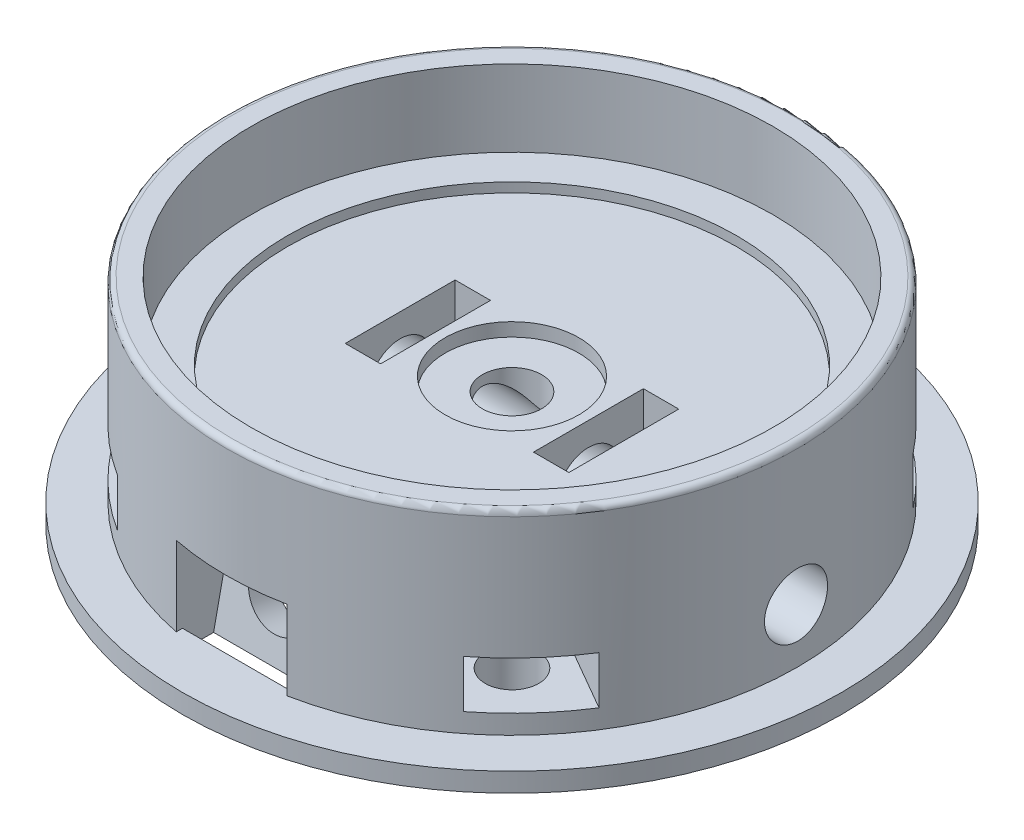
SolidWorks part; units mm, degrees
ref_plane "Front Plane" through (0, 0, 0) normal (0, 0, 1) x (1, 0, 0)
ref_plane "Top Plane" through (0, 0, 0) normal (0, 1, 0) x (1, 0, 0)
ref_plane "Right Plane" through (0, 0, 0) normal (1, 0, 0) x (0, 0, -1)
sketch "Sketch1" plane through (0, 0, 0) normal (0, 1, 0) x (1, 0, 0)
  circle A0 centre (0, 0) radius 14.95
  dimension "D1" = 29.9
extrude "Boss-Extrude1" add sketch "Sketch1" along normal blind 6.2
sketch "Sketch2" plane through (0, 6.2, 0) normal (0, 1, 0) x (1, 0, 0)
  circle A0 centre (0, 0) radius 11.75
  dimension "D1" = 23.5
extrude "Cut-Extrude1" cut sketch "Sketch2" against normal blind 0.5
sketch "Sketch3" plane through (0, 6.2, 0) normal (0, 1, 0) x (1, 0, 0)
  circle A0 centre (0, 0) radius 13.65
  circle A1 centre (0, 0) radius 14.95
  circle A2 centre (0, 0) radius 14.95 construction
  dimension "D1" = 27.3
extrude "Boss-Extrude2" add sketch "Sketch3" along normal blind 4
fillet "Fillet1" radius 0.3 1 edges at (0, 10.2, 14.95)
sketch "Sketch4" plane through (0, 5.7, 0) normal (0, 1, 0) x (1, 0, 0)
  circle A0 centre (0, 0) radius 1.55
  dimension "D1" = 3.1
extrude "Cut-Extrude2" cut sketch "Sketch4" against normal through all
ref_plane "Plane1" through (4, 0, 0) normal (1, 0, 0) x (0, 0, -1)
sketch "Sketch5" plane through (0, 0, 0) normal (1, 0, 0) x (0, 0, -1)
  line L1 (1.55, 5.7) -> (-1.55, 5.7) construction
  line L2 (-2.875, -0.05) -> (2.875, -0.05) construction
  line L3 (-2.875, -0.05) -> (-2.875, 5.7) construction
  line L4 (-2.875, 5.7) -> (2.875, 5.7) construction
  line L5 (2.875, -0.05) -> (2.875, 5.7) construction
  line L6 (-2.875, -0.05) -> (2.875, 5.7) construction
  line L7 (-2.875, 5.7) -> (2.875, -0.05) construction
  circle A0 centre (0, 2.825) radius 1.65
  dimension "D1" = 3.3
  dimension "D2" = 5.75
extrude "Cut-Extrude3" cut sketch "Sketch5" along normal through all
sketch "Sketch6" plane through (0, 0, 0) normal (0, -1, 0) x (1, 0, 0)
  circle A0 centre (0, 0) radius 1.55 construction
  circle A1 centre (0, 0) radius 1.55
  circle A2 centre (0, 0) radius 17.25
  dimension "D1" = 34.5
extrude "Boss-Extrude3" add sketch "Sketch6" along normal blind 1
sketch "Sketch7" plane through (4, 0, 0) normal (1, 0, 0) x (0, 0, -1)
  line L7 (-2.875, 5.7) -> (2.875, 5.7)
  line L8 (-2.875, 5.7) -> (-2.875, -0.05)
  line L9 (-2.875, -0.05) -> (2.875, -0.05)
  line L10 (2.875, 5.7) -> (2.875, -0.05)
  line L11 (-2.875, 5.7) -> (2.875, -0.05) construction
  line L12 (-2.875, -0.05) -> (2.875, 5.7) construction
  point P1 (0, 2.825)
  dimension "D2" = 5.75
extrude "Cut-Extrude4" cut sketch "Sketch7" along normal blind 1.85
ref_axis "Axis1" through (0, 9.9, 0) along (0, -1, 0)
pattern_circular "CirPattern1" count 2 over 360 about axis through (0, 9.9, 0) along (0, -1, 0) of "Cut-Extrude4", "Cut-Extrude3"
ref_plane "Plane2" through (0, 0, 0) normal (0, 0, 1) x (0, -1, 0)
ref_plane "Plane3" through (0, 0, 12.5) normal (0, 0, 1) x (0, -1, 0)
sketch "Sketch11" plane through (0, 0, 12.5) normal (0, 0, 1) x (0, -1, 0)
  line L0 (0, 23.2225) -> (0, -23.2225) construction
  point P4 (0, 0)
ref_plane "Plane4" through (0, 2.5421, 11.9597) normal (0, 0.2079, 0.9781) x (-1, 0, 0)
sketch "Sketch9" plane through (0, 0.4189, 12.411) normal (0, 0.2079, 0.9781) x (0, -0.9781, 0.2079)
  line L0 (-11.8543, 0) -> (-2.1706, 0) construction
  line L2 (1.4283, 2.9) -> (-4.3717, 2.9) construction
  line L3 (1.4283, 2.9) -> (1.4283, -2.9) construction
  line L4 (1.4283, -2.9) -> (-4.3717, -2.9) construction
  line L5 (-4.3717, 2.9) -> (-4.3717, -2.9) construction
  line L6 (1.4283, 2.9) -> (-4.3717, -2.9) construction
  line L7 (1.4283, -2.9) -> (-4.3717, 2.9) construction
  line L8 (0.4283, 23.2225) -> (0.4283, -23.2225) construction
  circle A0 centre (-1.4717, 0) radius 1.65
  dimension "D2" = 3.3
  dimension "D1" = 5.8
  dimension "D3" = 1
extrude "Cut-Extrude5" cut sketch "Sketch9" along normal through all and the other way blind 2
sketch "Sketch10" plane through (0, 0, 12.5) normal (0, 0.2079, 0.9781) x (0, -0.9781, 0.2079)
  line L1 (1, 2.9) -> (-4.8, 2.9) construction
  line L2 (-4.8, 2.9) -> (-4.8, -2.9) construction
  line L3 (1, -2.9) -> (-4.8, -2.9) construction
  line L5 (1, 2.9) -> (-4.8, 2.9)
  line L6 (-4.8, 2.9) -> (-4.8, -2.9)
  line L7 (1, -2.9) -> (-4.8, -2.9)
  line L8 (1, 2.9) -> (3, 2.9)
  line L9 (3, 2.9) -> (3, -2.9)
  line L10 (3, -2.9) -> (1, -2.9)
  dimension "D1" = 2
extrude "Cut-Extrude6" cut sketch "Sketch10" along normal blind 1.8
ref_plane "Plane5" through (0, 2.2302, 10.4924) normal (0, 0.2079, 0.9781) x (-1, 0, 0)
sketch "Sketch13" plane through (0, 2.2302, 10.4924) normal (0, 0.2079, 0.9781) x (-1, 0, 0)
  line L0 (-2.4902, -0.2075) -> (-3.8756, 3.5989)
  line L1 (-3.8756, 3.5989) -> (3.8756, 3.5989)
  line L2 (3.8756, 3.5989) -> (2.4902, -0.2075)
  line L3 (0, 0.6989) -> (0, 3.5989) construction
  line L4 (-2.9, 3.5989) -> (2.9, 3.5989) construction
  circle A0 centre (0, 0.6989) radius 1.65 construction
  circle A1 centre (0, 0.6989) radius 1.65 construction
  circle A2 centre (0, 0.6989) radius 2.65 construction
  arc A3 (2.4902, -0.2075) -> (-2.4902, -0.2075) centre (0, 0.6989) cw
  dimension "D1" = 20
  dimension "D2" = 1
ref_plane "Plane6" through (0, 0, 0) normal (-1, 0, 0) x (0, -1, 0)
ref_plane "Plane7" through (0, 0, 14.95) normal (0, 0, 1) x (1, 0, 0)
sketch "Sketch14" plane through (0, 0, 0) normal (-1, 0, 0) x (0, -1, 0)
  line L0 (-3.1606, 10.2947) -> (3.2723, 0) construction
  line L3 (0.0673, 10.9808) -> (-3.1606, 10.2947) construction
  line L5 (-3.1606, 10.2947) -> (-0.9985, 0.1229) construction
  arc A0 (-3.1606, 10.2947) -> (3.2723, 0) centre (14.1981, 13.9844) ccw
  dimension "D1" = 70
sweep "Cut-Sweep1" cut profiles "Sketch13" path "Sketch14"
sketch "Sketch19" plane through (0, 0, 14.95) normal (0, 0, 1) x (1, 0, 0)
  line L0 (2.9, 5.0693) -> (-2.9, 5.0693) construction
  line L1 (2.9, 5.0693) -> (-2.9, 5.0693) construction
  line L2 (14.95, 0) -> (-14.95, 0) construction
  line L3 (2.9, 0) -> (-2.9, 0) construction
  line L4 (-2.9, 5.0693) -> (-2.9, 0) construction
  line L5 (2.9, 5.0693) -> (2.9, 0) construction
  line L6 (-2.9, 4.1501) -> (2.9, 4.1501)
  line L7 (2.9, 4.1501) -> (2.9, 0)
  line L8 (2.9, 0) -> (-2.9, 0)
  line L9 (-2.9, 0) -> (-2.9, 4.1501)
  spline S0 degree 3 poles (-0.1103, 0.7763) (0.2206, 0.7763) (0.4399, 0.8212) (0.8405, 0.99) (1.0254, 1.1159) (1.2535, 1.3495) (1.3227, 1.4364) (1.4409, 1.6192) (1.4907, 1.7158) (1.5713, 1.9192) (1.6018, 2.0256) (1.6413, 2.2393) (1.6508, 2.3478) (1.6481, 2.6782) (1.6047, 2.8939) (1.4812, 3.1989) (1.431, 3.2954) (1.313, 3.4783) (1.2443, 3.5654) (1.0179, 3.8015) (0.8351, 3.9301) (0.4362, 4.1039) (0.2169, 4.1502) (-0.1103, 4.15) (-0.221, 4.1383) (-0.434, 4.0932) (-0.5375, 4.06) (-0.8386, 3.9282) (-1.0184, 3.8015) (-1.2465, 3.5629) (-1.3137, 3.4773) (-1.4313, 3.2948) (-1.4822, 3.1968) (-1.5641, 2.9938) (-1.5952, 2.8896) (-1.6378, 2.6758) (-1.6492, 2.5653) (-1.6515, 2.2381) (-1.6108, 2.0182) (-1.4501, 1.6141) (-1.3285, 1.4262) (-1.1006, 1.193) (-1.0155, 1.1217) (-0.835, 0.9992) (-0.7396, 0.9473) (-0.5381, 0.8627) (-0.4321, 0.8302) (-0.2188, 0.7873) (-0.1103, 0.7763) (0.2206, 0.7763) (0.4399, 0.8212) knots -0.03125 -0.03125 0 0 0.0625 0.0625 0.125 0.125 0.15625 0.15625 0.1875 0.1875 0.21875 0.21875 0.25 0.25 0.3125 0.3125 0.34375 0.34375 0.375 0.375 0.4375 0.4375 0.5 0.5 0.53125 0.53125 0.5625 0.5625 0.625 0.625 0.65625 0.65625 0.6875 0.6875 0.71875 0.71875 0.75 0.75 0.8125 0.8125 0.875 0.875 0.90625 0.90625 0.9375 0.9375 0.96875 0.96875 1 1 1.0625 1.0625 1.125 only from (0, 0.7763) to (0, 0.7763) construction
  spline S1 degree 3 poles (-0.1103, 0.7763) (0.2206, 0.7763) (0.4399, 0.8212) (0.8405, 0.99) (1.0254, 1.1159) (1.2535, 1.3495) (1.3227, 1.4364) (1.4409, 1.6192) (1.4907, 1.7158) (1.5713, 1.9192) (1.6018, 2.0256) (1.6413, 2.2393) (1.6508, 2.3478) (1.6481, 2.6782) (1.6047, 2.8939) (1.4812, 3.1989) (1.431, 3.2954) (1.313, 3.4783) (1.2443, 3.5654) (1.0179, 3.8015) (0.8351, 3.9301) (0.4362, 4.1039) (0.2169, 4.1502) (-0.1103, 4.15) (-0.221, 4.1383) (-0.434, 4.0932) (-0.5375, 4.06) (-0.8386, 3.9282) (-1.0184, 3.8015) (-1.2465, 3.5629) (-1.3137, 3.4773) (-1.4313, 3.2948) (-1.4822, 3.1968) (-1.5641, 2.9938) (-1.5952, 2.8896) (-1.6378, 2.6758) (-1.6492, 2.5653) (-1.6515, 2.2381) (-1.6108, 2.0182) (-1.4501, 1.6141) (-1.3285, 1.4262) (-1.1006, 1.193) (-1.0155, 1.1217) (-0.835, 0.9992) (-0.7396, 0.9473) (-0.5381, 0.8627) (-0.4321, 0.8302) (-0.2188, 0.7873) (-0.1103, 0.7763) (0.2206, 0.7763) (0.4399, 0.8212) knots -0.03125 -0.03125 0 0 0.0625 0.0625 0.125 0.125 0.15625 0.15625 0.1875 0.1875 0.21875 0.21875 0.25 0.25 0.3125 0.3125 0.34375 0.34375 0.375 0.375 0.4375 0.4375 0.5 0.5 0.53125 0.53125 0.5625 0.5625 0.625 0.625 0.65625 0.65625 0.6875 0.6875 0.71875 0.71875 0.75 0.75 0.8125 0.8125 0.875 0.875 0.90625 0.90625 0.9375 0.9375 0.96875 0.96875 1 1 1.0625 1.0625 1.125 only from (0, 0.7763) to (0, 0.7763) construction
extrude "Cut-Extrude11" cut sketch "Sketch19" against normal up to surface (0.6098 mm away) up to face at (0, 2.0347, 13.9077)
pattern_circular "CirPattern2" count 2 over 360 about axis through (0, 9.9, 0) along (0, -1, 0) of "Cut-Extrude5", "Cut-Sweep1", "Cut-Extrude6", "Cut-Extrude11"
sketch "Sketch16" plane through (0, -1, 0) normal (0, -1, 0) x (1, 0, 0)
  line L0 (0, 0) -> (-12.1976, 12.1976) construction
  line L1 (0, 11.1539) -> (0, -11.1539) construction
  circle A0 centre (0, 0) radius 17.25 construction
  circle A1 centre (-8.5206, 8.5206) radius 1.4
  circle A2 centre (-8.5206, 8.5206) radius 2.9 construction
  circle A3 centre (0, 0) radius 14.95 construction
  dimension "D2" = 2.8
  dimension "D3" = 5.8
  dimension "D1" = 45
extrude "Cut-Extrude8" cut sketch "Sketch16" against normal blind 4.5
sketch "Sketch17" plane through (0, 3.5, 0) normal (0, -1, 0) x (1, 0, 0)
  line L0 (0, 11.1539) -> (0, -11.1539) construction
  line L1 (-9.9351, 10.9706) -> (-11.3497, 8.5206) construction
  line L2 (-11.3497, 8.5206) -> (-9.9351, 6.0706)
  line L3 (-9.9351, 6.0706) -> (-7.1061, 6.0706)
  line L4 (-7.1061, 6.0706) -> (-5.6916, 8.5206)
  line L5 (-5.6916, 8.5206) -> (-7.1061, 10.9706)
  line L6 (-7.1061, 10.9706) -> (-9.9351, 10.9706) construction
  line L7 (-7.1061, 10.9706) -> (-8.0542, 12.6127)
  line L8 (-8.0542, 12.6127) -> (-12.2977, 10.1627)
  line L9 (-12.2977, 10.1627) -> (-11.3497, 8.5206)
  circle A0 centre (-8.5206, 8.5206) radius 2.45 construction
  circle A1 centre (0, 0) radius 14.95 construction
  dimension "D1" = 4.9
  dimension "D2" = 30
extrude "Cut-Extrude9" cut sketch "Sketch17" along normal blind 2.5
pattern_circular "CirPattern3" count 4 over 360 about axis through (0, 9.9, 0) along (0, -1, 0) of "Cut-Extrude8", "Cut-Extrude9"
sketch "Sketch18" plane through (0, 5.7, 0) normal (0, 1, 0) x (1, 0, 0)
  circle A2 centre (0, 0) radius 3.5
  dimension "D1" = 7
extrude "Cut-Extrude10" cut sketch "Sketch18" against normal blind 0.7
